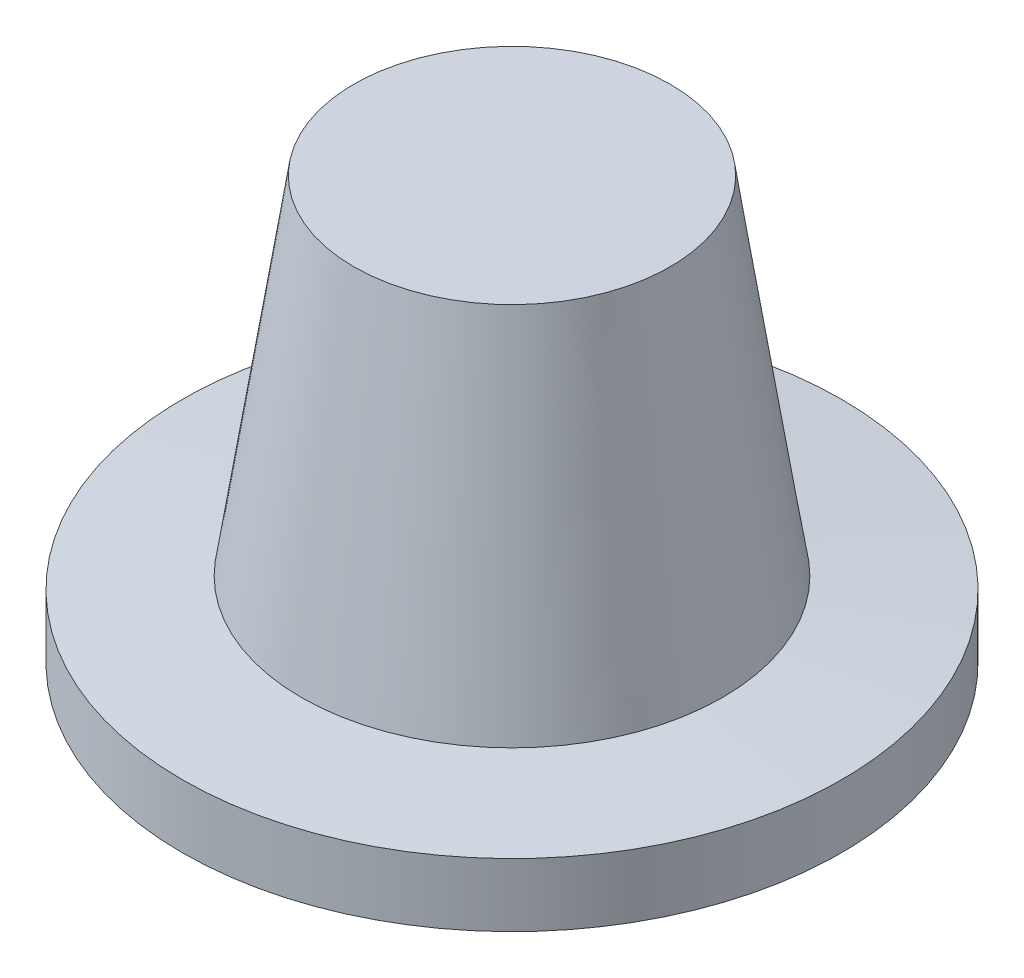
SolidWorks part; units mm, degrees
ref_plane "Front Plane" through (0, 0, 0) normal (0, 0, 1) x (1, 0, 0)
ref_plane "Top Plane" through (0, 0, 0) normal (0, 1, 0) x (1, 0, 0)
ref_plane "Right Plane" through (0, 0, 0) normal (1, 0, 0) x (0, 0, -1)
sketch "Sketch1" plane through (0, 0, 0) normal (0, 0, 1) x (1, 0, 0)
  line L0 (0, 0) -> (0, 56.6533) construction
  line L1 (0, 4.572) -> (3.175, 4.572)
  line L2 (3.175, 4.572) -> (3.175, 0)
  line L3 (3.175, 0) -> (7.9375, 0)
  line L4 (7.9375, 0) -> (7.9375, 1.524)
  line L5 (7.9375, 1.524) -> (5.0731, 1.8081)
  line L6 (5.0731, 1.8081) -> (3.81, 10.16)
  line L7 (3.81, 10.16) -> (0, 10.16)
  line L8 (0, 10.16) -> (0, 4.572)
  dimension "D1" = 15.875
  dimension "D2" = 6.35
  dimension "D3" = 7.62
  dimension "D4" = 1.524
  dimension "D5" = 10.16
  dimension "D6" = 4.572
revolve "Revolve1" add sketch "Sketch1" angle 360 about L0
